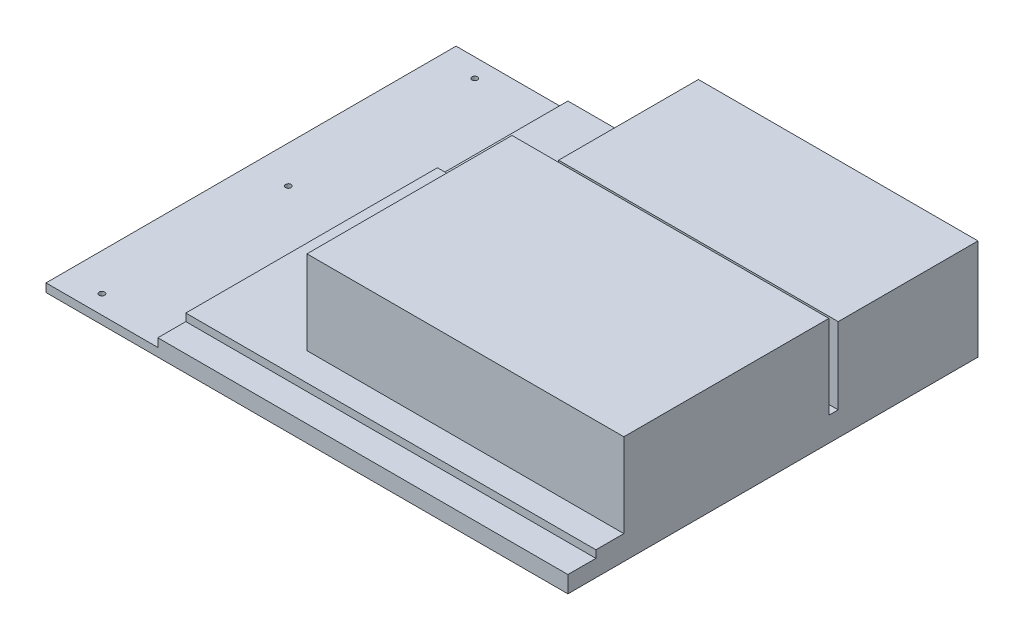
SolidWorks part; units mm, degrees
material "Perspex (TM) GS Acrylic Cast Sheet"
ref_plane "Front Plane" through (0, 0, 0) normal (0, 0, 1) x (1, 0, 0)
ref_plane "Top Plane" through (0, 0, 0) normal (0, 1, 0) x (1, 0, 0)
ref_plane "Right Plane" through (0, 0, 0) normal (1, 0, 0) x (0, 0, -1)
sketch "Sketch1" plane through (0, 0, 0) normal (0, 1, 0) x (1, 0, 0)
  line L1 (-128.3019, 71.5094) -> (91.6981, 71.5094)
  line L2 (-128.3019, 71.5094) -> (-128.3019, -148.4906)
  line L3 (-128.3019, -148.4906) -> (91.6981, -148.4906)
  line L4 (91.6981, 71.5094) -> (91.6981, -148.4906)
  dimension "D1" = 220
  dimension "D2" = 220
extrude "Boss-Extrude1" add sketch "Sketch1" along normal blind 4.5
sketch "Sketch2" plane through (0, 4.5, 0) normal (0, 1, 0) x (1, 0, 0)
  line L0 (-128.3019, -133.4906) -> (91.6981, -133.4906)
  line L1 (-128.3019, 71.5094) -> (-128.3019, -148.4906) construction
  line L2 (91.6981, -148.4906) -> (91.6981, 71.5094) construction
  line L3 (91.6981, -133.4906) -> (91.6981, 1.5094)
  line L4 (91.6981, 1.5094) -> (-128.3019, 1.5094)
  line L5 (-128.3019, 1.5094) -> (-128.3019, -133.4906)
  line L6 (-128.3019, -148.4906) -> (91.6981, -148.4906) construction
  dimension "D1" = 15
  dimension "D2" = 150
extrude "Boss-Extrude2" add sketch "Sketch2" along normal blind 4
sketch "Sketch3" plane through (0, 4.5, 0) normal (0, 1, 0) x (1, 0, 0)
  line L0 (91.6981, 1.5094) -> (91.6981, 71.5094) construction
  line L1 (-58.3019, 71.5094) -> (91.6981, 71.5094)
  line L2 (-58.3019, 71.5094) -> (-58.3019, -3.4906)
  line L3 (-58.3019, -3.4906) -> (91.6981, -3.4906)
  line L4 (91.6981, 71.5094) -> (91.6981, -3.4906)
  line L5 (91.6981, 71.5094) -> (-128.3019, 71.5094) construction
  dimension "D1" = 150
  dimension "D2" = 75
extrude "Boss-Extrude3" add sketch "Sketch3" along normal blind 45
sketch "Sketch4" plane through (0, 8.5, 0) normal (0, 1, 0) x (1, 0, 0)
  line L0 (91.6981, -133.4906) -> (91.6981, -3.4906) construction
  line L1 (-78.3019, -8.4906) -> (91.6981, -8.4906)
  line L2 (-78.3019, -8.4906) -> (-78.3019, -118.4906)
  line L3 (-78.3019, -118.4906) -> (91.6981, -118.4906)
  line L4 (91.6981, -8.4906) -> (91.6981, -118.4906)
  line L5 (-128.3019, -148.4906) -> (91.6981, -148.4906) construction
  dimension "D1" = 170
  dimension "D2" = 140
  dimension "D3" = 110
extrude "Boss-Extrude4" add sketch "Sketch4" along normal blind 45
sketch "Sketch5" plane through (0, 0, 0) normal (0, -1, 0) x (1, 0, 0)
  line L0 (91.6981, -71.5094) -> (-128.3019, -71.5094) construction
  line L1 (91.6981, 148.4906) -> (-188.3019, 148.4906)
  line L2 (91.6981, 148.4906) -> (91.6981, -71.5094)
  line L3 (91.6981, -71.5094) -> (-188.3019, -71.5094)
  line L4 (-188.3019, 148.4906) -> (-188.3019, -71.5094)
  line L5 (-128.3019, -71.5094) -> (-128.3019, 148.4906) construction
  dimension "D1" = 60
extrude "Boss-Extrude5" add sketch "Sketch5" along normal blind 4.5 contours L4 L3 L2 L1
sketch "Sketch6" plane through (0, 0, 0) normal (0, 1, 0) x (1, 0, 0)
  line L0 (-128.3019, 71.5094) -> (-188.3019, 71.5094) construction
  line L1 (-188.3019, -148.4906) -> (-188.3019, 71.5094) construction
  line L2 (-128.3019, -148.4906) -> (-188.3019, -148.4906) construction
  circle A0 centre (-168.3019, 61.5094) radius 1.5
  circle A1 centre (-168.3019, -138.4906) radius 1.5
  circle A2 centre (-168.3019, -38.4906) radius 1.5
  dimension "D1" = 3
  dimension "D2" = 10
  dimension "D3" = 20
  dimension "D4" = 10
  dimension "D5" = 110
extrude "Cut-Extrude1" cut sketch "Sketch6" against normal blind 10
